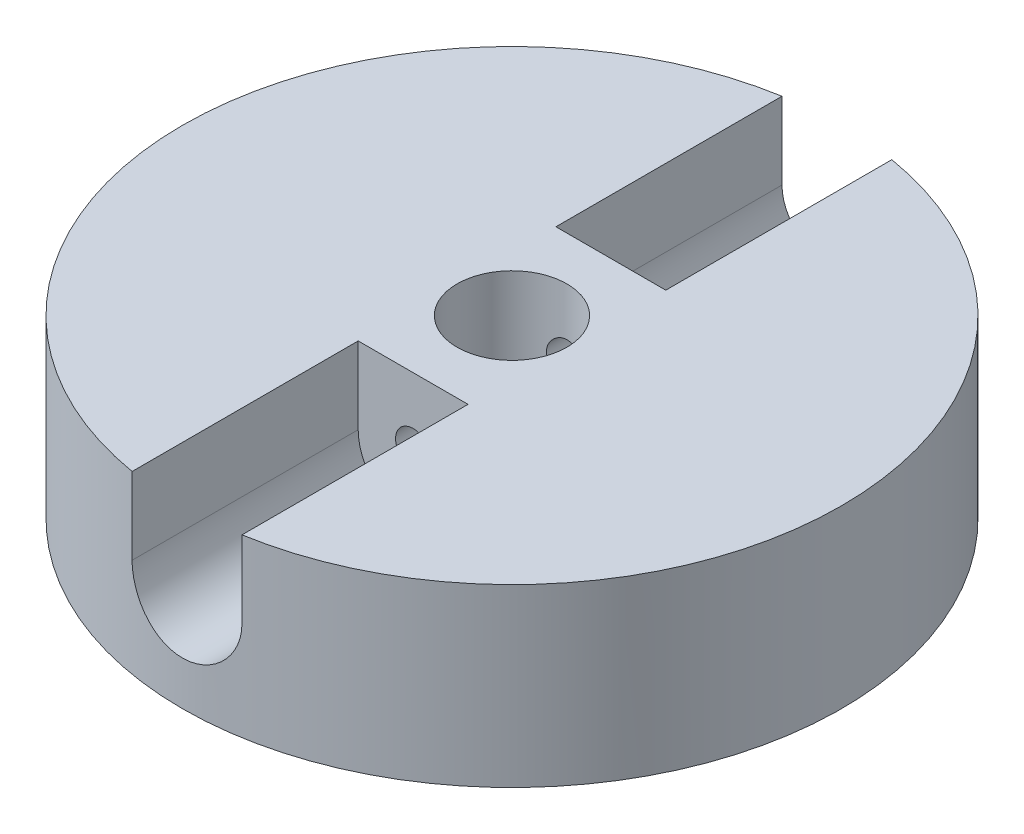
SolidWorks part; units mm, degrees
ref_plane "Front Plane" through (0, 0, 0) normal (0, 0, 1) x (1, 0, 0)
ref_plane "Top Plane" through (0, 0, 0) normal (0, 1, 0) x (1, 0, 0)
ref_plane "Right Plane" through (0, 0, 0) normal (1, 0, 0) x (0, 0, -1)
sketch "Sketch2" plane through (0, 0, 0) normal (0, 1, 0) x (1, 0, 0)
  circle A0 centre (0, 0) radius 15
  dimension "D1" = 30
extrude "Boss-Extrude1" add sketch "Sketch2" along normal blind 8
sketch "Sketch3" plane through (0, 8, 0) normal (0, 1, 0) x (1, 0, 0)
  circle A0 centre (0, 0) radius 12.5
  circle A1 centre (0, 0) radius 2.5
  dimension "D1" = 25
  dimension "D2" = 5
ref_plane "Plane1" through (0, 0, 4.5) normal (0, 0, 1) x (1, 0, 0)
ref_plane "Plane2" through (0, 0, 20) normal (0, 0, 1) x (1, 0, 0)
sketch "Sketch9" plane through (0, 0, 20) normal (0, 0, 1) x (1, 0, 0)
  line L0 (2.5, 0) -> (2.5, 2)
  line L1 (0, 0) -> (2.5, 0)
  line L2 (0, 0) -> (0, 8)
  line L3 (0, 8) -> (2.5, 8)
  line L4 (2.5, 0) -> (2.5, 8)
  line L5 (0, 8) -> (-2.5, 8)
  line L6 (-2.5, 8) -> (-2.5, 0)
  line L7 (-2.5, 0) -> (0, 0)
  line L8 (2.5, 2) -> (-2.5, 2)
  arc A0 (-2.5, 4.5) -> (2.5, 4.5) centre (0, 4.5) ccw
  dimension "D6" = 2.5
  dimension "D1" = 2
  dimension "D2" = 8
  dimension "D3" = 2.5
  dimension "D4" = 8
  dimension "D5" = 2.5
extrude "Cut-Extrude8" cut sketch "Sketch9" against normal blind 15.5 contours L8 L2 L5 L6 | L8 L4 L3 L2 region at (1.1821, 5.2398, 20) region at (-1.1821, 5.2398, 20)
ref_plane "Plane3" through (0, 0, -4.5) normal (0, 0, 1) x (1, 0, 0)
sketch "Sketch10" plane through (0, 0, -4.5) normal (0, 0, 1) x (1, 0, 0)
  line L1 (0, 0) -> (-2.5, 0)
  line L2 (0, 0) -> (0, 8)
  line L3 (0, 8) -> (-2.5, 8)
  line L4 (-2.5, 0) -> (-2.5, 8)
  line L5 (0, 0) -> (2.5, 0)
  line L6 (0, 0) -> (0, 8)
  line L7 (0, 8) -> (2.5, 8)
  line L8 (2.5, 0) -> (2.5, 8)
  arc A0 (-2.5, 4.5) -> (2.5, 4.5) centre (0, 4.5) ccw
  dimension "D5" = 4.5
  dimension "D1" = 8
  dimension "D2" = 2.5
  dimension "D3" = 2.5
  dimension "D4" = 8
extrude "Cut-Extrude15" cut sketch "Sketch10" against normal blind 18 contours L6 A0 L8 L7 | L4 A0 L6 L3 region at (-1.1821, 5.2398, -4.5) region at (1.1821, 5.2398, -4.5)
sketch "Sketch7" plane through (0, 0, 4.5) normal (0, 0, 1) x (1, 0, 0)
  line L0 (0, 0) -> (0, 5)
  circle A0 centre (0, 5) radius 1
  dimension "D1" = 5
extrude "Cut-Extrude16" cut sketch "Sketch3" against normal blind 6 contours A1 region at (0, 8, 0)
sketch "Sketch12" plane through (0, 0, 0) normal (0, -1, 0) x (1, 0, 0)
  line L0 (0, 0) -> (-10, 0)
  line L1 (0, 0) -> (-7.0711, 7.0711)
  circle A0 centre (-7.0711, 7.0711) radius 1.5
  circle A1 centre (7.0711, 7.0711) radius 1.5
  circle A2 centre (7.0711, -7.0711) radius 1.5
  circle A3 centre (-7.0711, -7.0711) radius 1.5
  point P14 (0, 0)
  dimension "D4" = 4
  dimension "D1" = 10
  dimension "D2" = 10
  dimension "D3" = 45
hole_wizard "M3 Tapped Hole2" positions "Sketch15" profile "Sketch16" tap size "M3" standard "ISO"
sketch "Sketch15" plane through (0, 0, 0) normal (0, -1, 0) x (-1, 0, 0)
  point P0 (7.0711, -7.0711)
  point P3 (-7.0711, -7.0711)
  point P6 (-7.0711, 7.0711)
  point P9 (7.0711, 7.0711)
sketch "Sketch16" plane through (-7.0711, 0, 7.0711) normal (1, 0, 0) x (0, 0, -1)
  line L0 (0, 0) -> (0, 3.2511)
  line L1 (0, 3.2511) -> (1.25, 2.5)
  line L2 (1.25, 2.5) -> (1.25, 0)
  line L5 (1.25, 0) -> (0, 0)
  line L10 (0, 3.2511) -> (-1.25, 2.5) construction
  line L11 (0, -6.35) -> (0, 107.95) construction
  dimension "Tap Drill Dia." = 2.5
  dimension "Tap Drill Depth" = 2.5
  dimension "Drill Angle" = 118
cosmetic thread "Hole Thread5" parameters "D1"=1, "D2"=3
cosmetic thread "Hole Thread6" parameters "D1"=1, "D2"=3
cosmetic thread "Hole Thread7" parameters "D1"=1, "D2"=3
cosmetic thread "Hole Thread8" parameters "D1"=1, "D2"=3
hole_wizard "M2 Tapped Hole1" positions "Sketch19" profile "Sketch20" tap size "M2" standard "ISO" end condition through all
sketch "Sketch19" plane through (0, 0, 4.5) normal (0, 0, 1) x (1, 0, 0)
  point P0 (0, 5)
cosmetic thread "Hole Thread9" parameters "D2"=2
sketch "Sketch20" plane through (0, 5, 4.5) normal (1, 0, 0) x (0, -1, 0)
  line L0 (0, 0) -> (0, 19.5)
  line L1 (0, 19.5) -> (0.8, 19.5)
  line L2 (0.8, 19.5) -> (0.8, 0)
  line L5 (0.8, 0) -> (0, 0)
  line L11 (0, -6.35) -> (0, 107.95) construction
  dimension "Thru Tap Drill Dia." = 1.6
  dimension "Thru Tap Drill Depth" = 19.5
